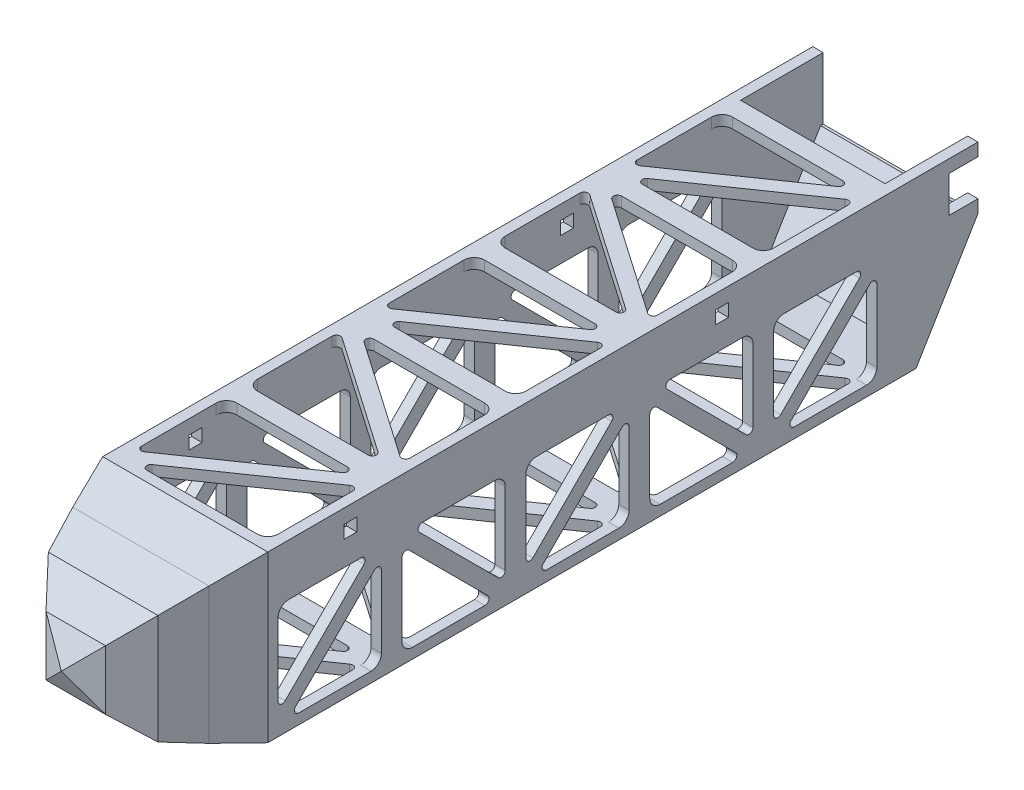
SolidWorks part; units mm, degrees
material "Balsa"
ref_plane "Front Plane" through (0, 0, 0) normal (0, 0, 1) x (1, 0, 0)
ref_plane "Top Plane" through (0, 0, 0) normal (0, 1, 0) x (1, 0, 0)
ref_plane "Right Plane" through (0, 0, 0) normal (1, 0, 0) x (0, 0, -1)
sketch "Sketch1" plane through (0, 0, 0) normal (0, 0, 1) x (1, 0, 0)
  line L1 (-50.8, -50.8) -> (50.8, -50.8)
  line L2 (-50.8, -50.8) -> (-50.8, 50.8)
  line L3 (-50.8, 50.8) -> (50.8, 50.8)
  line L4 (50.8, -50.8) -> (50.8, 50.8)
  line L5 (-50.8, -50.8) -> (50.8, 50.8) construction
  line L6 (-50.8, 50.8) -> (50.8, -50.8) construction
  point P0 (0, 0)
  dimension "D1" = 101.6
extrude "Boss-Extrude1" add sketch "Sketch1" along normal blind 436.88 contours L2 L1 L4 L3
ref_plane "Plane1" through (0, 0, 464.1566) normal (0, 0, 1) x (1, 0, 0)
sketch "Sketch3" plane through (0, 0, 464.1566) normal (0, 0, 1) x (1, 0, 0)
  line L1 (-41.9373, -41.9373) -> (41.9373, -41.9373)
  line L2 (-41.9373, -41.9373) -> (-41.9373, 41.9373)
  line L3 (-41.9373, 41.9373) -> (41.9373, 41.9373)
  line L4 (41.9373, -41.9373) -> (41.9373, 41.9373)
  line L5 (-41.9373, -41.9373) -> (41.9373, 41.9373) construction
  line L6 (-41.9373, 41.9373) -> (41.9373, -41.9373) construction
  point P0 (0, 0)
  dimension "D1" = 83.8746
  dimension "D2" = 83.8746
sketch "Sketch5" plane through (0, 0, 436.88) normal (0, 0, 1) x (1, 0, 0)
  line L0 (50.8, -50.8) -> (50.8, 50.8) construction
  line L1 (-50.8, 50.8) -> (50.8, 50.8) construction
  line L2 (-50.8, -50.8) -> (-50.8, 50.8) construction
  line L3 (-50.8, -50.8) -> (50.8, -50.8) construction
  line L4 (50.8, -50.8) -> (50.8, 50.8)
  line L5 (-50.8, 50.8) -> (50.8, 50.8)
  line L6 (-50.8, -50.8) -> (-50.8, 50.8)
  line L7 (-50.8, -50.8) -> (50.8, -50.8)
  dimension "D1" = 101.6
  dimension "D2" = 101.6
loft "Loft2" add profiles "Sketch5", "Sketch3" connector at (-50.8, 50.8, 436.88) connector at (-41.9373, 41.9373, 464.1566)
ref_plane "Plane2" through (0, 0, 487.3594) normal (0, 0, 1) x (1, 0, 0)
sketch "Sketch6" plane through (0, 0, 487.3594) normal (0, 0, 1) x (1, 0, 0)
  line L1 (-33.716, -33.716) -> (33.716, -33.716)
  line L2 (-33.716, -33.716) -> (-33.716, 33.716)
  line L3 (-33.716, 33.716) -> (33.716, 33.716)
  line L4 (33.716, -33.716) -> (33.716, 33.716)
  line L5 (-33.716, -33.716) -> (33.716, 33.716) construction
  line L6 (-33.716, 33.716) -> (33.716, -33.716) construction
  point P0 (0, 0)
loft "Loft3" add profiles "Sketch3<6>", "Sketch6" connector at (-41.9373, 41.9373, 464.1566) connector at (-33.716, 33.716, 487.3594)
sketch "Sketch3<6>" plane through (0, 0, 464.1566) normal (0, 0, 1) x (1, 0, 0) same geometry as "Sketch3"
ref_plane "Plane3" through (0, 0, 504.2173) normal (0, 0, 1) x (1, 0, 0)
sketch "Sketch7" plane through (0, 0, 504.2173) normal (0, 0, 1) x (1, 0, 0)
  line L5 (-41.9373, -41.9373) -> (41.9373, 41.9373) construction
  line L6 (-18.3041, -18.3041) -> (18.3041, -18.3041)
  line L8 (-18.3041, -18.3041) -> (-18.3041, 18.3041)
  line L9 (-18.3041, 18.3041) -> (18.3041, 18.3041)
  line L10 (18.3041, -18.3041) -> (18.3041, 18.3041)
  line L11 (-18.3041, -18.3041) -> (18.3041, 18.3041) construction
  line L12 (-18.3041, 18.3041) -> (18.3041, -18.3041) construction
  point P1 (0, 0)
loft "Loft4" add profiles "Sketch6<4>", "Sketch7" connector at (33.716, 33.716, 487.3594) connector at (18.3041, 18.3041, 504.2173)
sketch "Sketch6<4>" plane through (0, 0, 487.3594) normal (0, 0, 1) x (1, 0, 0) same geometry as "Sketch6"
sketch3d "3DSketch1" plane through (0, 0, 0) normal (0, 0, 1) x (1, 0, 0)
  dimension "D1" = 8.8627
sketch "Sketch8" plane through (0, 0, 513.08) normal (0, 0, 1) x (1, 0, 0)
  point P0 (0, 0)
loft "Loft5" add profiles "Sketch8", "Sketch7<5>"
sketch "Sketch7<5>" plane through (0, 0, 504.2173) normal (0, 0, 1) x (1, 0, 0) same geometry as "Sketch7"
shell "Shell1" thickness 6.35 removed face at (0, 0, 0)
sketch "Sketch9" plane through (50.8, 0, 0) normal (1, 0, 0) x (0, 0, -1)
  line L0 (-436.88, 50.8) -> (-436.88, 38.1)
  line L1 (-436.88, -50.8) -> (-436.88, 50.8) construction
  line L2 (-436.88, 38.1) -> (-386.08, 38.1)
  line L3 (-386.08, 38.1) -> (-157.48, 38.1)
  line L5 (-390.0805, 34.0995) -> (-382.0795, 34.0995)
  line L6 (-390.0805, 34.0995) -> (-390.0805, 42.1005)
  line L7 (-390.0805, 42.1005) -> (-382.0795, 42.1005)
  line L8 (-382.0795, 34.0995) -> (-382.0795, 42.1005)
  line L9 (-390.0805, 34.0995) -> (-382.0795, 42.1005) construction
  line L10 (-390.0805, 42.1005) -> (-382.0795, 34.0995) construction
  line L11 (-161.4805, 34.0995) -> (-153.4795, 34.0995)
  line L12 (-161.4805, 34.0995) -> (-161.4805, 42.1005)
  line L13 (-161.4805, 42.1005) -> (-153.4795, 42.1005)
  line L14 (-153.4795, 34.0995) -> (-153.4795, 42.1005)
  line L15 (-161.4805, 34.0995) -> (-153.4795, 42.1005) construction
  line L16 (-161.4805, 42.1005) -> (-153.4795, 34.0995) construction
  dimension "D4" = 8.001
  dimension "D5" = 8.001
  dimension "D1" = 12.7
  dimension "D2" = 50.8
  dimension "D3" = 228.6
  dimension "D6" = 8.001
  dimension "D7" = 8.001
extrude "Cut-Extrude1" cut sketch "Sketch9" against normal through all contours L5 L8 L3 L2 L6 | L3 L8 L7 L6 L2 | L11 L14 L13 L12 region at (50.8, 40.1002, 386.08) region at (50.8, 36.0997, 386.08) region at (50.8, 40.1002, 161.3673)
sketch "Sketch10" plane through (50.8, 0, 0) normal (1, 0, 0) x (0, 0, -1)
  line L0 (-436.88, 50.8) -> (0, 50.8) construction
  line L3 (0, 50.8) -> (-68.9584, 50.8)
  line L4 (-68.9584, -50.8) -> (-68.9584, 50.8)
  line L5 (0, 50.8) -> (0, 12.7)
  line L6 (0, -50.8) -> (-38.1, -50.8)
  line L7 (0, 12.7) -> (-38.1, -50.8)
  line L8 (0, 12.7) -> (0, -50.8)
  line M16 (0, -50.8) -> (0, 50.8)
  line M19 (-436.88, -50.8) -> (0, -50.8)
  dimension "D1" = 38.1
  dimension "D2" = 38.1
  dimension "D3" = 63.5
extrude "Cut-Extrude2" cut sketch "Sketch10" against normal through all contours L7 M16 M19 region at (50.8, -29.6333, 12.7)
sketch "Sketch11" plane through (50.8, 0, 0) normal (1, 0, 0) x (0, 0, -1)
  line L0 (-38.1, -50.8) -> (-39.6875, -50.8)
  line L1 (-436.88, -50.8) -> (-38.1, -50.8) construction
  line L2 (0, 50.8) -> (-1.5875, 50.8)
  line L3 (-436.88, 50.8) -> (0, 50.8) construction
  line L4 (-1.5875, 50.8) -> (-1.5875, 12.7)
  line L5 (0, 50.8) -> (0, 12.7)
  line L6 (-1.5875, 12.7) -> (-39.6875, -50.8)
  line L7 (0, 12.7) -> (-38.1, -50.8)
  dimension "D1" = 1.5875
  dimension "D2" = 1.5875
extrude "Boss-Extrude2" add sketch "Sketch11" against normal blind 101.6
sketch "Sketch12" plane through (0, 0, 0) normal (0, 0, -1) x (-1, 0, 0)
  line L0 (-50.8, 50.8) -> (-44.45, 50.8)
  line L1 (50.8, 50.8) -> (-50.8, 50.8) construction
  line L2 (50.8, 12.7) -> (-50.8, 12.7) construction
  line L3 (-44.45, 50.8) -> (44.45, 50.8)
  line L4 (-44.45, 50.8) -> (-44.45, 12.7)
  line L5 (-44.45, 12.7) -> (44.45, 12.7)
  line L6 (44.45, 50.8) -> (44.45, 12.7)
  line M7 (-50.8, 12.7) -> (50.8, 12.7)
  line M9 (50.8, 50.8) -> (-50.8, 50.8)
  dimension "D1" = 6.35
  dimension "D2" = 88.9
extrude "Cut-Extrude3" cut sketch "Sketch12" against normal blind 50.8 contours L6 L4 M9 M7 region at (0, 31.75, 0)
sketch "Sketch15" plane through (50.8, 0, 0) normal (1, 0, 0) x (0, 0, -1)
  line L0 (0, 12.7) -> (0, 50.8) construction
  line L1 (0, 42.926) -> (-17.78, 42.926)
  line L2 (0, 42.926) -> (0, 20.574)
  line L3 (0, 20.574) -> (-17.78, 20.574)
  line L4 (-17.78, 42.926) -> (-17.78, 20.574)
  line L5 (-436.88, 50.8) -> (0, 50.8) construction
  dimension "D1" = 17.78
  dimension "D2" = 22.352
  dimension "D3" = 7.874
extrude "Cut-Extrude5" cut sketch "Sketch15" against normal up to surface (6.35 mm away)
sketch "Sketch16" plane through (50.8, 0, 0) normal (1, 0, 0) x (0, 0, -1)
  line L0 (-436.88, -50.8) -> (-436.88, 50.8) construction
  line L1 (-424.18, 19.05) -> (-379.5121, 19.05)
  line L2 (-430.53, 12.7) -> (-430.53, -31.9679)
  line L3 (-418.0479, -44.45) -> (-373.38, -44.45)
  line L4 (-367.03, 6.5679) -> (-367.03, -38.1)
  line L5 (-436.88, -50.8) -> (-38.1, -50.8) construction
  line L6 (-354.33, 6.5679) -> (-354.33, -38.1)
  line L7 (-341.8479, 19.05) -> (-297.18, 19.05)
  line L8 (-290.83, 12.7) -> (-290.83, -31.9679)
  line L9 (-347.98, -44.45) -> (-303.3121, -44.45)
  line L10 (-278.13, 12.7) -> (-278.13, -31.9679)
  line L11 (-271.78, 19.05) -> (-227.1121, 19.05)
  line L12 (-214.63, 6.5679) -> (-214.63, -38.1)
  line L13 (-265.6479, -44.45) -> (-220.98, -44.45)
  line L14 (-201.93, 6.5679) -> (-201.93, -38.1)
  line L15 (-189.4479, 19.05) -> (-144.78, 19.05)
  line L16 (-138.43, 12.7) -> (-138.43, -31.9679)
  line L17 (-195.58, -44.45) -> (-150.9121, -44.45)
  line L18 (-125.73, 12.7) -> (-125.73, -31.9679)
  line L19 (-119.38, 19.05) -> (-74.7121, 19.05)
  line L20 (-62.23, 6.5679) -> (-62.23, -38.1)
  line L21 (-113.2479, -44.45) -> (-68.58, -44.45)
  line L22 (-377.7161, 14.7139) -> (-426.1939, -33.7639)
  line L23 (-419.8439, -40.1139) -> (-371.3661, 8.3639)
  line L24 (-349.9939, 8.3639) -> (-301.5161, -40.1139)
  line L25 (-343.6439, 14.7139) -> (-295.1661, -33.7639)
  line L26 (-273.7939, -33.7639) -> (-225.3161, 14.7139)
  line L27 (-218.9661, 8.3639) -> (-267.4439, -40.1139)
  line L28 (-197.5939, 8.3639) -> (-149.1161, -40.1139)
  line L29 (-142.7661, -33.7639) -> (-191.2439, 14.7139)
  line L30 (-121.3939, -33.7639) -> (-72.9161, 14.7139)
  line L31 (-66.5661, 8.3639) -> (-115.0439, -40.1139)
  arc A0 (-430.53, -38.1) -> (-424.18, -44.45) centre (-424.18, -38.1) ccw
  arc A1 (-373.38, -44.45) -> (-367.03, -38.1) centre (-373.38, -38.1) ccw
  arc A2 (-373.38, 19.05) -> (-367.03, 12.7) centre (-373.38, 12.7) cw
  arc A3 (-424.18, 19.05) -> (-430.53, 12.7) centre (-424.18, 12.7) ccw
  arc A4 (-347.98, 19.05) -> (-354.33, 12.7) centre (-347.98, 12.7) ccw
  arc A5 (-354.33, -38.1) -> (-347.98, -44.45) centre (-347.98, -38.1) ccw
  arc A6 (-297.18, 19.05) -> (-290.83, 12.7) centre (-297.18, 12.7) cw
  arc A7 (-297.18, -44.45) -> (-290.83, -38.1) centre (-297.18, -38.1) ccw
  arc A8 (-271.78, 19.05) -> (-278.13, 12.7) centre (-271.78, 12.7) ccw
  arc A9 (-278.13, -38.1) -> (-271.78, -44.45) centre (-271.78, -38.1) ccw
  arc A10 (-220.98, 19.05) -> (-214.63, 12.7) centre (-220.98, 12.7) cw
  arc A11 (-220.98, -44.45) -> (-214.63, -38.1) centre (-220.98, -38.1) ccw
  arc A12 (-195.58, 19.05) -> (-201.93, 12.7) centre (-195.58, 12.7) ccw
  arc A13 (-201.93, -38.1) -> (-195.58, -44.45) centre (-195.58, -38.1) ccw
  arc A14 (-144.78, 19.05) -> (-138.43, 12.7) centre (-144.78, 12.7) cw
  arc A15 (-144.78, -44.45) -> (-138.43, -38.1) centre (-144.78, -38.1) ccw
  arc A16 (-119.38, 19.05) -> (-125.73, 12.7) centre (-119.38, 12.7) ccw
  arc A17 (-125.73, -38.1) -> (-119.38, -44.45) centre (-119.38, -38.1) ccw
  arc A18 (-68.58, 19.05) -> (-62.23, 12.7) centre (-68.58, 12.7) cw
  arc A19 (-68.58, -44.45) -> (-62.23, -38.1) centre (-68.58, -38.1) ccw
  arc A20 (-74.7121, 19.05) -> (-72.9161, 14.7139) centre (-74.7121, 16.51) cw
  arc A21 (-66.5661, 8.3639) -> (-62.23, 6.5679) centre (-64.77, 6.5679) cw
  arc A22 (-115.0439, -40.1139) -> (-113.2479, -44.45) centre (-113.2479, -41.91) ccw
  arc A23 (-121.3939, -33.7639) -> (-125.73, -31.9679) centre (-123.19, -31.9679) cw
  arc A24 (-150.9121, -44.45) -> (-149.1161, -40.1139) centre (-150.9121, -41.91) ccw
  arc A25 (-142.7661, -33.7639) -> (-138.43, -31.9679) centre (-140.97, -31.9679) ccw
  arc A26 (-189.4479, 19.05) -> (-191.2439, 14.7139) centre (-189.4479, 16.51) ccw
  arc A27 (-197.5939, 8.3639) -> (-201.93, 6.5679) centre (-199.39, 6.5679) ccw
  arc A28 (-227.1121, 19.05) -> (-225.3161, 14.7139) centre (-227.1121, 16.51) cw
  arc A29 (-218.9661, 8.3639) -> (-214.63, 6.5679) centre (-217.17, 6.5679) cw
  arc A30 (-265.6479, -44.45) -> (-267.4439, -40.1139) centre (-265.6479, -41.91) cw
  arc A31 (-278.13, -31.9679) -> (-273.7939, -33.7639) centre (-275.59, -31.9679) ccw
  arc A32 (-303.3121, -44.45) -> (-301.5161, -40.1139) centre (-303.3121, -41.91) ccw
  arc A33 (-290.83, -31.9679) -> (-295.1661, -33.7639) centre (-293.37, -31.9679) cw
  arc A34 (-341.8479, 19.05) -> (-343.6439, 14.7139) centre (-341.8479, 16.51) ccw
  arc A35 (-349.9939, 8.3639) -> (-354.33, 6.5679) centre (-351.79, 6.5679) ccw
  arc A36 (-367.03, 6.5679) -> (-371.3661, 8.3639) centre (-369.57, 6.5679) ccw
  arc A37 (-418.0479, -44.45) -> (-419.8439, -40.1139) centre (-418.0479, -41.91) cw
  arc A38 (-377.7161, 14.7139) -> (-379.5121, 19.05) centre (-379.5121, 16.51) ccw
  arc A39 (-426.1939, -33.7639) -> (-430.53, -31.9679) centre (-427.99, -31.9679) cw
  point P12 (-367.03, -44.45)
  point P15 (-367.03, 19.05)
  point P18 (-430.53, 19.05)
  dimension "D1" = 6.35
  dimension "D5" = 6.35
  dimension "D7" = 2.54
  dimension "D2" = 6.35
  dimension "D3" = 63.5
  dimension "D4" = 63.5
  dimension "D6" = 5
extrude "Cut-Extrude6" cut sketch "Sketch16" against normal up to surface (101.6 mm away) contours L1 A3 L2 L22 | L3 A1 L4 L23 | L6 A5 L9 L24 | A6 L7 L25 L8 | L11 A8 L10 L26 | L13 A11 L12 L27 | L14 A13 L17 L28 | A14 L15 L29 L16 | L21 A19 L20 L31 | L19 A16 L18 L30 region at (50.8, -0.0083, 411.4717) region at (50.8, -25.3917, 386.0883) region at (50.8, -25.3917, 335.2717) region at (50.8, -0.0083, 309.8883) region at (50.8, -0.0083, 259.0717) region at (50.8, -25.3917, 233.6883) region at (50.8, -25.3917, 182.8717) region at (50.8, -0.0083, 157.4883) region at (50.8, -0.0083, 106.6717) region at (50.8, -25.3917, 81.2883) up to face at (-50.8, 2.54, 182.372)
sketch "Sketch17" plane through (0, 50.8, 0) normal (0, 1, 0) x (1, 0, 0)
  line L0 (50.8, -436.88) -> (50.8, 0) construction
  line L1 (38.1, -430.53) -> (-22.2093, -430.53)
  line L2 (44.45, -424.18) -> (44.45, -382.8539)
  line L3 (22.2093, -367.03) -> (-38.1, -367.03)
  line L4 (-44.45, -414.7061) -> (-44.45, -373.38)
  line L5 (-50.8, -436.88) -> (50.8, -436.88) construction
  line L6 (-50.8, -436.88) -> (-50.8, 0) construction
  line L7 (44.45, -343.2236) -> (44.45, -301.8976)
  line L8 (22.2093, -359.0476) -> (-38.1, -359.0476)
  line L9 (-44.45, -352.6976) -> (-44.45, -303.2798)
  line L11 (44.45, -281.2151) -> (44.45, -231.7973)
  line L12 (38.1, -287.5651) -> (-35.7816, -287.5651)
  line L13 (-44.45, -279.8329) -> (-44.45, -230.4151)
  line L14 (37.8738, -224.0651) -> (-38.1, -224.0651)
  line L15 (44.45, -208.3504) -> (44.45, -158.9327)
  line L16 (35.7816, -216.0827) -> (-38.1, -216.0827)
  line L17 (-44.45, -209.7327) -> (-44.45, -160.3149)
  line L19 (44.45, -138.2502) -> (44.45, -92.298)
  line L20 (38.1, -144.6002) -> (-37.3066, -144.6002)
  line L21 (-44.45, -133.4025) -> (-44.45, -87.4502)
  line L22 (29.9688, -81.1002) -> (-38.1, -81.1002)
  line L23 (-36.6606, -418.7874) -> (25.0348, -376.0751)
  line L24 (38.1, -367.03) -> (44.45, -373.38)
  line L25 (-25.0348, -421.4849) -> (36.6606, -378.7726)
  line L26 (36.6606, -347.3049) -> (-31.4146, -300.1759)
  line L27 (-43.3135, -302.6843) -> (25.0348, -350.0024)
  line L28 (-36.1938, -286.2454) -> (43.3135, -231.2019)
  line L29 (38.286, -223.9363) -> (-43.3135, -280.4283)
  line L30 (36.1938, -214.763) -> (-43.3135, -159.7194)
  line L31 (-31.4146, -157.211) -> (43.3135, -208.9459)
  line L32 (-38.7524, -145.0519) -> (40.4642, -90.2096)
  line L33 (31.4146, -85.7286) -> (-40.4642, -135.4908)
  line L35 (38.1, -152.5827) -> (-37.3066, -152.5827) [skipped]
  line L36 (38.1, -152.5827) -> (35.6588, -124.1581)
  line L37 (-29.9688, -152.5827) -> (38.1, -152.5827)
  line L38 (-29.9688, -295.5476) -> (38.1, -295.5476)
  line L39 (38.1, -295.5476) -> (-36.5494, -295.5476) [skipped]
  arc A0 (44.45, -373.38) -> (38.1, -367.03) centre (38.1, -373.38) ccw
  arc A1 (38.1, -430.53) -> (44.45, -424.18) centre (38.1, -424.18) ccw
  arc A2 (-38.1, -430.53) -> (-44.45, -424.18) centre (-38.1, -424.18) cw
  arc A3 (-38.1, -367.03) -> (-44.45, -373.38) centre (-38.1, -373.38) ccw
  arc A4 (38.1, -359.0476) -> (44.45, -352.6976) centre (38.1, -352.6976) ccw
  arc A5 (44.45, -301.8976) -> (38.1, -295.5476) centre (38.1, -301.8976) ccw
  arc A6 (-38.1, -359.0476) -> (-44.45, -352.6976) centre (-38.1, -352.6976) cw
  arc A7 (-38.1, -295.5476) -> (-44.45, -301.8976) centre (-38.1, -301.8976) ccw
  arc A8 (38.1, -287.5651) -> (44.45, -281.2151) centre (38.1, -281.2151) ccw
  arc A9 (44.45, -230.4151) -> (38.1, -224.0651) centre (38.1, -230.4151) ccw
  arc A10 (-38.1, -287.5651) -> (-44.45, -281.2151) centre (-38.1, -281.2151) cw
  arc A11 (-38.1, -224.0651) -> (-44.45, -230.4151) centre (-38.1, -230.4151) ccw
  arc A12 (38.1, -216.0827) -> (44.45, -209.7327) centre (38.1, -209.7327) ccw
  arc A13 (44.45, -158.9327) -> (38.1, -152.5827) centre (38.1, -158.9327) ccw
  arc A14 (-38.1, -216.0827) -> (-44.45, -209.7327) centre (-38.1, -209.7327) cw
  arc A16 (38.1, -144.6002) -> (44.45, -138.2502) centre (38.1, -138.2502) ccw
  arc A17 (44.45, -87.4502) -> (38.1, -81.1002) centre (38.1, -87.4502) ccw
  arc A18 (-38.1, -144.6002) -> (-44.45, -138.2502) centre (-38.1, -138.2502) cw
  arc A19 (-38.1, -81.1002) -> (-44.45, -87.4502) centre (-38.1, -87.4502) ccw
  arc A20 (-40.4642, -135.4908) -> (-44.45, -133.4025) centre (-41.91, -133.4025) cw
  arc A21 (31.4146, -85.7286) -> (29.9688, -81.1002) centre (29.9688, -83.6402) ccw
  arc A22 (40.4642, -90.2096) -> (44.45, -92.298) centre (41.91, -92.298) cw
  arc A23 (-38.7524, -145.0519) -> (-37.3066, -144.6002) centre (-37.3066, -147.1402) ccw
  arc A25 (-43.3135, -159.7194) -> (-44.45, -160.3149) centre (-43.7258, -160.3149) ccw
  arc A26 (44.45, -208.3504) -> (43.3135, -208.9459) centre (43.7258, -208.3504) cw
  arc A27 (36.1938, -214.763) -> (35.7816, -216.0827) centre (35.7816, -215.3584) cw
  arc A28 (37.8738, -224.0651) -> (38.286, -223.9363) centre (37.8738, -223.3409) cw
  arc A29 (43.3135, -231.2019) -> (44.45, -231.7973) centre (43.7258, -231.7973) cw
  arc A30 (-35.7816, -287.5651) -> (-36.1938, -286.2454) centre (-35.7816, -286.8409) cw
  arc A31 (-43.3135, -280.4283) -> (-44.45, -279.8329) centre (-43.7258, -279.8329) cw
  arc A32 (-44.45, -303.2798) -> (-43.3135, -302.6843) centre (-43.7258, -303.2798) cw
  arc A34 (44.45, -343.2236) -> (36.6606, -347.3049) centre (39.4861, -343.2236) cw
  arc A35 (22.2093, -359.0476) -> (25.0348, -350.0024) centre (22.2093, -354.0837) ccw
  arc A36 (44.45, -382.8539) -> (36.6606, -378.7726) centre (39.4861, -382.8539) ccw
  arc A37 (25.0348, -376.0751) -> (22.2093, -367.03) centre (22.2093, -371.9939) ccw
  arc A38 (-44.45, -414.7061) -> (-36.6606, -418.7874) centre (-39.4861, -414.7061) ccw
  arc A39 (-22.2093, -430.53) -> (-25.0348, -421.4849) centre (-22.2093, -425.5661) cw
  arc A40 (-38.1, -152.5827) -> (-44.45, -158.9327) centre (-38.1, -158.9327) ccw [skipped]
  arc A41 (-31.4146, -157.211) -> (-29.9688, -152.5827) centre (-29.9688, -155.1227) cw
  arc A42 (-31.4146, -300.1759) -> (-29.9688, -295.5476) centre (-29.9688, -298.0876) cw
  point P16 (-44.45, -430.53)
  point P19 (-44.45, -367.03)
  dimension "D1" = 6.35
  dimension "D5" = 6.35
  dimension "D7" = 2.54
  dimension "D2" = 6.35
  dimension "D4" = 63.5
  dimension "D6" = 5
  dimension "D8" = 2.54
  dimension "D9" = 2.54
  dimension "D3" = 6.35
sketch "Sketch18" plane through (0, 50.8, 0) normal (0, 1, 0) x (1, 0, 0)
  line L0 (-50.8, -436.88) -> (-50.8, 0) construction
  line L1 (38.1, -430.53) -> (-29.9688, -430.53)
  line L2 (44.45, -424.18) -> (44.45, -378.2278)
  line L3 (29.9688, -367.03) -> (-38.1, -367.03)
  line L4 (-44.45, -419.3322) -> (-44.45, -373.38)
  line L5 (50.8, -436.88) -> (50.8, 0) construction
  line L6 (-50.8, -436.88) -> (50.8, -436.88) construction
  line L7 (-40.4642, -299.9394) -> (31.4146, -349.7016)
  line L8 (-38.1, -354.33) -> (29.9688, -354.33)
  line L9 (-44.45, -347.98) -> (-44.45, -302.0278)
  line L10 (-29.9688, -290.83) -> (38.1, -290.83)
  line L11 (44.45, -343.1322) -> (44.45, -297.18)
  line L12 (40.4642, -345.2206) -> (-31.4146, -295.4584)
  line L13 (31.4146, -371.6584) -> (-40.4642, -421.4206)
  line L14 (-31.4146, -425.9016) -> (40.4642, -376.1394)
  line L15 (38.1, -278.13) -> (-29.9688, -278.13)
  line L16 (44.45, -271.78) -> (44.45, -225.8278)
  line L17 (-31.4146, -273.5016) -> (40.4642, -223.7394)
  line L18 (31.4146, -219.2584) -> (-40.4642, -269.0206)
  line L19 (29.9688, -214.63) -> (-38.1, -214.63)
  line L20 (-44.45, -266.9322) -> (-44.45, -220.98)
  line L21 (-38.1, -201.93) -> (29.9688, -201.93)
  line L22 (-44.45, -195.58) -> (-44.45, -149.6278)
  line L23 (-40.4642, -147.5394) -> (31.4146, -197.3016)
  line L24 (40.4642, -192.8206) -> (-31.4146, -143.0584)
  line L25 (-29.9688, -138.43) -> (38.1, -138.43)
  line L26 (44.45, -190.7322) -> (44.45, -144.78)
  line L27 (38.1, -125.73) -> (-29.9688, -125.73)
  line L28 (44.45, -119.38) -> (44.45, -73.4278)
  line L29 (-31.4146, -121.1016) -> (40.4642, -71.3394)
  line L30 (31.4146, -66.8584) -> (-40.4642, -116.6206)
  line L31 (29.9688, -62.23) -> (-38.1, -62.23)
  line L32 (-44.45, -114.5322) -> (-44.45, -68.58)
  line L39 (-38.1, -49.53) -> (29.9688, -49.53) [skipped]
  line L40 (-40.4642, 4.8606) -> (31.4146, -44.9016) [skipped]
  line L41 (-44.45, -43.18) -> (-44.45, 2.7722) [skipped]
  line L42 (40.4642, -40.4206) -> (-31.4146, 9.3416) [skipped]
  line L43 (-29.9688, 13.97) -> (38.1, 13.97) [skipped]
  line L44 (44.45, -38.3322) -> (44.45, 7.62) [skipped]
  arc A0 (38.1, -430.53) -> (44.45, -424.18) centre (38.1, -424.18) ccw
  arc A3 (-38.1, -367.03) -> (-44.45, -373.38) centre (-38.1, -373.38) ccw
  arc A4 (-38.1, -354.33) -> (-44.45, -347.98) centre (-38.1, -347.98) cw
  arc A6 (38.1, -290.83) -> (44.45, -297.18) centre (38.1, -297.18) cw
  arc A8 (44.45, -343.1322) -> (40.4642, -345.2206) centre (41.91, -343.1322) cw
  arc A9 (-29.9688, -290.83) -> (-31.4146, -295.4584) centre (-29.9688, -293.37) ccw
  arc A10 (-44.45, -302.0278) -> (-40.4642, -299.9394) centre (-41.91, -302.0278) cw
  arc A11 (29.9688, -354.33) -> (31.4146, -349.7016) centre (29.9688, -351.79) ccw
  arc A12 (44.45, -378.2278) -> (40.4642, -376.1394) centre (41.91, -378.2278) ccw
  arc A13 (29.9688, -367.03) -> (31.4146, -371.6584) centre (29.9688, -369.57) cw
  arc A14 (-29.9688, -430.53) -> (-31.4146, -425.9016) centre (-29.9688, -427.99) cw
  arc A15 (-44.45, -419.3322) -> (-40.4642, -421.4206) centre (-41.91, -419.3322) ccw
  arc A16 (-29.9688, -278.13) -> (-31.4146, -273.5016) centre (-29.9688, -275.59) cw
  arc A17 (38.1, -278.13) -> (44.45, -271.78) centre (38.1, -271.78) ccw
  arc A18 (44.45, -225.8278) -> (40.4642, -223.7394) centre (41.91, -225.8278) ccw
  arc A19 (-44.45, -266.9322) -> (-40.4642, -269.0206) centre (-41.91, -266.9322) ccw
  arc A20 (29.9688, -214.63) -> (31.4146, -219.2584) centre (29.9688, -217.17) cw
  arc A21 (-38.1, -214.63) -> (-44.45, -220.98) centre (-38.1, -220.98) ccw
  arc A22 (29.9688, -201.93) -> (31.4146, -197.3016) centre (29.9688, -199.39) ccw
  arc A23 (-38.1, -201.93) -> (-44.45, -195.58) centre (-38.1, -195.58) cw
  arc A24 (-44.45, -149.6278) -> (-40.4642, -147.5394) centre (-41.91, -149.6278) cw
  arc A25 (-29.9688, -138.43) -> (-31.4146, -143.0584) centre (-29.9688, -140.97) ccw
  arc A26 (44.45, -190.7322) -> (40.4642, -192.8206) centre (41.91, -190.7322) cw
  arc A27 (38.1, -138.43) -> (44.45, -144.78) centre (38.1, -144.78) cw
  arc A28 (-29.9688, -125.73) -> (-31.4146, -121.1016) centre (-29.9688, -123.19) cw
  arc A29 (38.1, -125.73) -> (44.45, -119.38) centre (38.1, -119.38) ccw
  arc A30 (44.45, -73.4278) -> (40.4642, -71.3394) centre (41.91, -73.4278) ccw
  arc A31 (-44.45, -114.5322) -> (-40.4642, -116.6206) centre (-41.91, -114.5322) ccw
  arc A32 (29.9688, -62.23) -> (31.4146, -66.8584) centre (29.9688, -64.77) cw
  arc A33 (-38.1, -62.23) -> (-44.45, -68.58) centre (-38.1, -68.58) ccw
  arc A40 (29.9688, -49.53) -> (31.4146, -44.9016) centre (29.9688, -46.99) ccw [skipped]
  arc A41 (-44.45, 2.7722) -> (-40.4642, 4.8606) centre (-41.91, 2.7722) cw [skipped]
  arc A42 (-38.1, -49.53) -> (-44.45, -43.18) centre (-38.1, -43.18) cw [skipped]
  arc A43 (-29.9688, 13.97) -> (-31.4146, 9.3416) centre (-29.9688, 11.43) ccw [skipped]
  arc A44 (38.1, 13.97) -> (44.45, 7.62) centre (38.1, 7.62) cw [skipped]
  arc A45 (44.45, -38.3322) -> (40.4642, -40.4206) centre (41.91, -38.3322) cw [skipped]
  point P12 (44.45, -430.53)
  point P15 (44.45, -367.03)
  point P28 (44.45, -354.33)
  point P31 (44.45, -290.83)
  dimension "D1" = 6.35
  dimension "D5" = 6.35
  dimension "D2" = 6.35
  dimension "D4" = 63.5
  dimension "D3" = 6.35
  dimension "D10" = 6.35
  dimension "D11" = 2.54
  dimension "D6" = 12.7
  dimension "D8" = 6.35
  dimension "D9" = 6.35
  dimension "D12" = 3
extrude "Cut-Extrude9" cut sketch "Sketch18" against normal up to surface (101.6 mm away) up to face at (0, -50.8, 237.49)
equation "\"Fuse_Diam\"= 4"
equation "\"D2@Sketch1\"=\"Fuse_Diam\""
equation "\"D1@Sketch1\"=\"Fuse_Diam\""
equation "\"Magic Line\"= 3 / ( cos ( 18 ) + cos ( 2 * 18 ) + cos ( 3 * 18 ) + cos ( 4 * 18 ) )"
equation "\"Second Stage Cone\"= 3.30215"
equation "\"D1@Sketch3\"=\"Second Stage Cone\""
equation "\"D2@Sketch3\"=\"Second Stage Cone\""
equation "\"Thick\"=0.25"
equation "\"D1@Sketch12\"=\"Thick\""
equation "\"D1@Shell1\"=\"Thick\""
equation "\"attachment\"=3.5"
equation "\"D2@Sketch12\"=\"attachment\""
equation "\"D2@Sketch16\"=\"Thick\""
equation "\"D1@Sketch16\"=0.25in"
equation "\"D1@Sketch17\"=\"Thick\""
equation "\"D2@Sketch17\"=\"Thick\""
equation "\"D3@Sketch17\"=\"Thick\""
equation "\"D1@Sketch18\"=\"Thick\""
equation "\"D2@Sketch18\"=\"Thick\""
